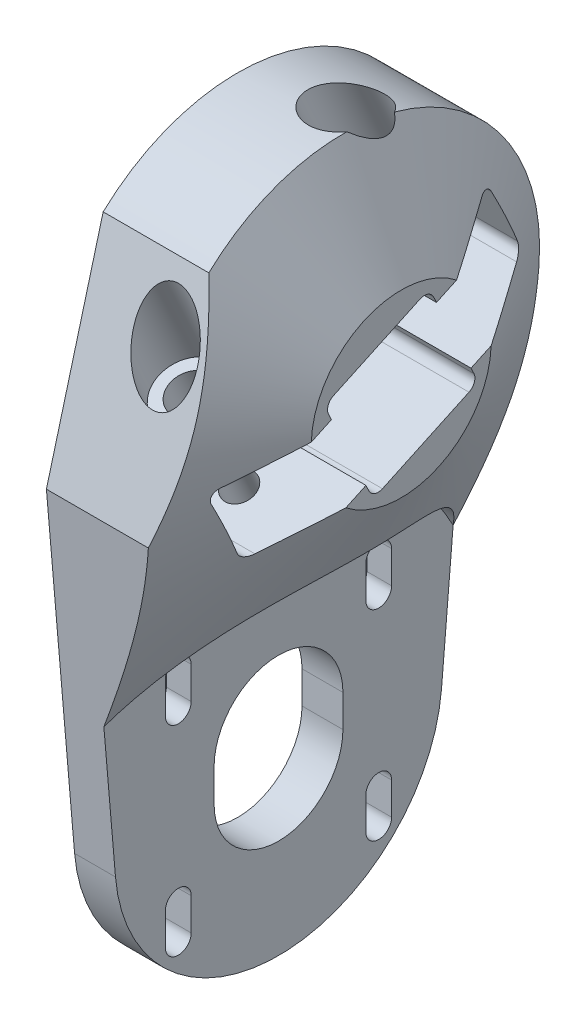
SolidWorks part; units mm, degrees
ref_plane "Front Plane" through (0, 0, 0) normal (0, 0, 1) x (1, 0, 0)
ref_plane "Top Plane" through (0, 0, 0) normal (0, 1, 0) x (1, 0, 0)
ref_plane "Right Plane" through (0, 0, 0) normal (1, 0, 0) x (0, 0, -1)
sketch "Sketch1" plane through (0, 0, 0) normal (1, 0, 0) x (0, 0, -1)
  line L0 (4.3532, 11.9603) -> (-11.9603, 4.3532)
  line L1 (4.3532, 11.9603) -> (11.9603, -4.3532)
  line L2 (-11.9603, 4.3532) -> (-4.3532, -11.9603)
  line L3 (11.9603, -4.3532) -> (-4.3532, -11.9603)
  line L4 (4.3532, 11.9603) -> (-4.3532, -11.9603) construction
  line L5 (-11.9603, 4.3532) -> (11.9603, -4.3532) construction
  line L6 (0, 0) -> (0, -57.15) construction
  line L7 (-30.3693, -2.5958) -> (-25.3077, -61.8132)
  line L8 (25.3077, -61.8132) -> (30.3693, -2.5958)
  line L9 (0, -57.15) -> (0, -103.9417) construction
  arc A0 (30.3693, -2.5958) -> (-30.3693, -2.5958) centre (0, 0) ccw
  arc A1 (-25.3077, -61.8132) -> (25.3077, -61.8132) centre (0, -59.65) ccw
  dimension "D1" = 2.5
  dimension "D2" = 30.48
  dimension "D6" = 57.15
  dimension "D7" = 25.4
  dimension "D8" = 0
  dimension "D3" = 18
  dimension "D4" = 18
  dimension "D5" = 25
extrude "Boss-Extrude1" add sketch "Sketch1" along normal blind 6.35 contours L7 A0 L1 L3 L2 L0 region at (0, -27.1671, 0)
sketch "Sketch19" plane through (6.35, 0, 0) normal (1, 0, 0) x (0, 0, -1)
  line L0 (0, -59.65) -> (0, -54.65)
  line L1 (0, -54.65) -> (15.5563, -39.0937) construction
  line L2 (15.5563, -44.0937) -> (15.5563, -39.0937) construction
  line L3 (13.5563, -44.0937) -> (13.5563, -39.0937)
  line L4 (17.5563, -44.0937) -> (17.5563, -39.0937)
  line L5 (-10, -59.65) -> (-10, -54.65)
  line L6 (10, -59.65) -> (10, -54.65)
  line L7 (0, -57.15) -> (7.4061, -57.15) construction
  line L8 (15.5563, -44.0937) -> (0, -59.65) construction
  line L9 (17.5563, -70.2063) -> (17.5563, -75.2063)
  line L10 (13.5563, -70.2063) -> (13.5563, -75.2063)
  line L11 (-17.5563, -44.0937) -> (-17.5563, -39.0937)
  line L12 (-13.5563, -44.0937) -> (-13.5563, -39.0937)
  line L13 (-13.5563, -70.2063) -> (-13.5563, -75.2063)
  line L14 (-17.5563, -70.2063) -> (-17.5563, -75.2063)
  line L15 (-15.5563, -44.0937) -> (0, -59.65) construction
  line L16 (0, -59.65) -> (-15.5563, -75.2063) construction
  line L17 (0, -59.65) -> (15.5563, -75.2063) construction
  arc A0 (-25.3077, -61.8132) -> (25.3077, -61.8132) centre (0, -59.65) ccw construction
  arc A1 (-25.3077, -61.8132) -> (25.3077, -61.8132) centre (0, -59.65) ccw
  arc A2 (-10, -59.65) -> (10, -59.65) centre (0, -59.65) ccw
  arc A3 (17.5563, -75.2063) -> (13.5563, -75.2063) centre (15.5563, -75.2063) cw
  arc A4 (13.5563, -70.2063) -> (17.5563, -70.2063) centre (15.5563, -70.2063) cw
  arc A6 (17.5563, -39.0937) -> (13.5563, -39.0937) centre (15.5563, -39.0937) ccw
  arc A7 (13.5563, -44.0937) -> (17.5563, -44.0937) centre (15.5563, -44.0937) ccw
  arc A8 (-17.5563, -39.0937) -> (-13.5563, -39.0937) centre (-15.5563, -39.0937) cw
  arc A9 (10, -54.65) -> (-10, -54.65) centre (0, -54.65) ccw
  arc A10 (-13.5563, -44.0937) -> (-17.5563, -44.0937) centre (-15.5563, -44.0937) cw
  arc A11 (-13.5563, -70.2063) -> (-17.5563, -70.2063) centre (-15.5563, -70.2063) ccw
  arc A13 (-17.5563, -75.2063) -> (-13.5563, -75.2063) centre (-15.5563, -75.2063) ccw
  point P8 (0, -57.15)
  dimension "D1" = 135
  dimension "D3" = 22
  dimension "D5" = 4
  dimension "D6" = 5
  dimension "D4" = 4
  dimension "D8" = 0
  dimension "D2" = 5
  dimension "D7" = 45
extrude "Cut-Extrude18" cut sketch "Sketch19" against normal blind 10 contours L6 A9 L5 A2 | A10 L12 A8 L11 | L14 A13 L13 A11 | A4 L10 A3 L9 | L4 A6 L3 A7 region at (6.35, -57.15, 9.6798) region at (6.35, -72.7063, -15.5563) region at (6.35, -41.5937, 15.5563) region at (6.35, -72.7063, 15.5563)
sketch "Sketch20" plane through (6.35, 0, 0) normal (1, 0, 0) x (0, 0, -1)
  circle A0 centre (0, 0) radius 57.15
  arc A1 (-25.3077, -61.8132) -> (25.3077, -61.8132) centre (0, -59.65) ccw construction
  point P3 (0, -85.05)
extrude "Boss-Extrude5" add sketch "Sketch20" along normal blind 19.05
sketch "Sketch21" plane through (0, 0, 0) normal (-1, 0, 0) x (0, 0, 1)
  line L0 (-24.435, 4.3878) -> (-10.8404, -1.9515)
  line L1 (11.9603, 4.3532) -> (4.3532, -11.9603) construction
  line L3 (-4.3532, 11.9603) -> (-11.9603, -4.3532) construction
  line L4 (-4.3532, 11.9603) -> (11.9603, 4.3532) construction
  line L5 (11.9603, 4.3532) -> (10.8404, 1.9515)
  line L7 (-4.3532, 11.9603) -> (-5.4731, 9.5586)
  line L8 (-4.3532, 11.9603) -> (11.9603, 4.3532)
  line L9 (-21.7514, 10.1428) -> (-25.3766, 11.8333) construction
  line L10 (19.0678, -15.8979) -> (5.4731, -9.5586)
  line L11 (19.0678, -15.8979) -> (24.435, -4.3878)
  line L12 (-24.435, 4.3878) -> (-19.0678, 15.8979)
  line L13 (24.435, -4.3878) -> (10.8404, 1.9515)
  line L16 (4.3532, -11.9603) -> (5.4731, -9.5586)
  line L17 (-11.9603, -4.3532) -> (-10.8404, -1.9515)
  line L18 (11.9603, 4.3532) -> (-4.3532, 11.9603)
  line L21 (-10.8404, -1.9515) -> (-11.9603, -4.3532)
  line L24 (-10.8404, -1.9515) -> (-24.435, 4.3878)
  line L27 (-5.4731, 9.5586) -> (-4.3532, 11.9603)
  line L29 (-5.4731, 9.5586) -> (-19.0678, 15.8979)
  line L30 (5.4731, -9.5586) -> (4.3532, -11.9603)
  line L31 (10.8404, 1.9515) -> (11.9603, 4.3532)
  line M13 (-11.9603, -4.3532) -> (-4.3532, 11.9603)
  line M14 (-4.3532, 11.9603) -> (11.9603, 4.3532)
  line M15 (11.9603, 4.3532) -> (4.3532, -11.9603)
  line M16 (4.3532, -11.9603) -> (-11.9603, -4.3532)
  dimension "D1" = 15
  dimension "D2" = 12.7
extrude "Cut-Extrude14" cut sketch "Sketch21" against normal through all contours L29 L12 L0 M13 | M13 M16 M15 M14 | L11 L13 L10 M15 region at (0, 6.9732, -14.9541) region at (0, 0, 0) region at (0, -6.9732, 14.9541)
sketch "Sketch22" plane through (0, 5.7551, 2.6836) normal (0, -0.9063, -0.4226) x (-1, 0, 0)
  line L0 (-25.4, -9) -> (0, -9) construction
  line L2 (0, -28.6209) -> (0, 30.48) construction
  circle A0 centre (-12.5, -16.5) radius 3.175
  dimension "D2" = 12.5
  dimension "D3" = 6.35
  dimension "D1" = 7.5
extrude "Cut-Extrude15" cut sketch "Sketch22" against normal through all
ref_plane "Plane1" through (0, 10.3591, 4.8305) normal (0, -0.9063, -0.4226) x (-1, 0, 0)
sketch "Sketch24" plane through (0, 10.3591, 4.8305) normal (0, -0.9063, -0.4226) x (-1, 0, 0)
  circle A0 centre (-12.5, -16.5) radius 5
  dimension "D1" = 10
extrude "Cut-Extrude16" cut sketch "Sketch24" against normal through all
sketch "Sketch25" plane through (0, -5.7551, -2.6836) normal (0, 0.9063, 0.4226) x (1, 0, 0)
  circle A0 centre (12.5, -16.5) radius 3.175 construction
  circle A1 centre (12.5, -16.5) radius 3.175
  circle A2 centre (12.5, -16.5) radius 2.3813
  dimension "D1" = 0.7937
extrude "Cut-Extrude17" cut sketch "Sketch25" against normal blind 10 contours A2 region at (12.5, -12.7283, 12.2705)
ref_plane "Plane2" through (0, 0, 0) normal (0, 0.4226, -0.9063) x (-1, 0, 0)
mirror "Mirror1" about plane through (0, 0, 0) normal (0, 0.4226, -0.9063) of "Cut-Extrude17", "Cut-Extrude15", "Cut-Extrude16"
mirror "Mirror2" about plane through (0, 0, 0) normal (1, 0, 0) of bodies 124 126
delete or keep bodies "Body-Delete/Keep 1" type delete bodies bodies 127
chamfer "Chamfer2" distance 2.5 angle 45 8 edges at (0, -46.0937, 15.5563) (0, -41.5937, 13.5563) (0, -37.0937, 15.5563) (0, -41.5937, 17.5563) (0, -46.0937, -15.5563) (0, -41.5937, -17.5563) (0, -41.5937, -13.5563) (0, -37.0937, -15.5563)
sketch "Sketch26" plane through (0, 0, 0) normal (-1, 0, 0) x (0, 0, 1)
  line L0 (11.4538, -58.2291) -> (27.0119, -8.4408)
  line L1 (0, 0) -> (0, -54.65) construction
  circle A0 centre (0, -54.65) radius 12
  circle A1 centre (0, 0) radius 28.3
  dimension "D1" = 24
  dimension "D2" = 56.6
fillet "Fillet1" radius 1.5875 8 edges at (12.7, -4.3532, -11.9603) (12.7, 4.3878, -24.435) (12.7, 11.9603, -4.3532) (12.7, 15.8979, -19.0678) (12.7, -4.3878, 24.435) (12.7, 4.3532, 11.9603) (12.7, -11.9603, 4.3532) (12.7, -15.8979, 19.0678)
sketch "Sketch28" plane through (6.35, 0, 0) normal (1, 0, 0) x (0, 0, -1)
  arc A0 (-10, -54.65) -> (10, -54.65) centre (0, -54.65) ccw construction
  arc A1 (-10, -54.65) -> (10, -54.65) centre (0, -54.65) ccw
  circle A3 centre (0, -54.65) radius 30.48
extrude "Cut-Extrude19" cut sketch "Sketch28" along normal through all contours A3
sketch "Sketch29" plane through (25.4, 0, 0) normal (1, 0, 0) x (0, 0, -1)
  arc A1 (30.3693, -2.5958) -> (-30.3693, -2.5958) centre (0, 0) ccw construction
  arc A2 (30.3693, -2.5958) -> (-30.3693, -2.5958) centre (0, 0) ccw
  circle A3 centre (0, 0) radius 13.97
sketch "Sketch30" plane through (6.35, 0, 0) normal (1, 0, 0) x (0, 0, -1)
  circle A0 centre (0, 0) radius 48.9194
sketch "Sketch31" plane through (0, 0, 0) normal (0, 1, 0) x (1, 0, 0)
  line L0 (25.4, -13.97) -> (25.4, 13.97) construction
  line L1 (25.4, -13.97) -> (25.4, 13.97)
  line L2 (6.35, -48.9194) -> (6.35, 48.9194) construction
  line L3 (6.35, -48.9194) -> (6.35, 48.9194)
  line L4 (25.4, -13.97) -> (6.35, -48.9194)
  line L5 (6.35, -48.9194) -> (6.35, -59.9521)
  line L6 (6.35, -59.9521) -> (25.4, -59.9521)
  line L7 (25.4, -59.9521) -> (25.4, -13.97)
  line L8 (25.4, 0) -> (0, 0) construction
revolve "Cut-Revolve1" cut sketch "Sketch31" angle 360 about L8 region at (17.8212, 0, 43.9131)
sketch "Sketch32" plane through (6.35, 0, 0) normal (-1, 0, 0) x (0, 0, 1)
  line L0 (30.3693, -2.5958) -> (25.3077, -61.8132) construction
  line L1 (-25.3077, -61.8132) -> (-30.3693, -2.5958) construction
  line L2 (30.3693, -2.5958) -> (25.3077, -61.8132)
  line L3 (-25.3077, -61.8132) -> (-30.3693, -2.5958)
  arc A0 (30.3693, -2.5958) -> (-30.3693, -2.5958) centre (0, 0) ccw construction
  arc A1 (30.3693, -2.5958) -> (-30.3693, -2.5958) centre (0, 0) ccw
  circle A2 centre (0, 0) radius 48.9194 construction
  circle A3 centre (0, 0) radius 48.9194
  arc M2 (27.1106, -40.72) -> (-27.1106, -40.72) centre (0, 0) ccw
  line M3 (-27.1106, -40.72) -> (-30.3693, -2.5958)
  arc M4 (-30.3693, -2.5958) -> (30.3693, -2.5958) centre (0, 0) cw
  line M5 (30.3693, -2.5958) -> (27.1106, -40.72)
extrude "Cut-Extrude20" cut sketch "Sketch32" against normal through all contours M5 M2 M3 M4 region at (6.35, 31.8069, 0)
sketch "Sketch33" plane through (0, 0, 0) normal (-1, 0, 0) x (0, 0, 1)
  line L0 (30.3693, -2.5958) -> (25.3077, -61.8132) construction
  line L1 (30.3693, -2.5958) -> (25.3077, -61.8132)
  line L2 (29.6796, -10.6648) -> (20.8695, 22.2147)
  line L3 (22.9962, -3.7169) -> (10.8404, 1.9515) construction
  arc A0 (30.3693, -2.5958) -> (-30.3693, -2.5958) centre (0, 0) ccw construction
  arc A1 (30.3693, -2.5958) -> (-30.3693, -2.5958) centre (0, 0) ccw
  arc M35 (30.3693, -2.5958) -> (-30.3693, -2.5958) centre (0, 0) ccw
  dimension "D1" = 50
  dimension "D2" = 25.908
extrude "Cut-Extrude21" cut sketch "Sketch33" against normal through all contours L2 L1 M35 region at (0, 6.8897, 26.8598)
equation "\".75i\"=14.27"
